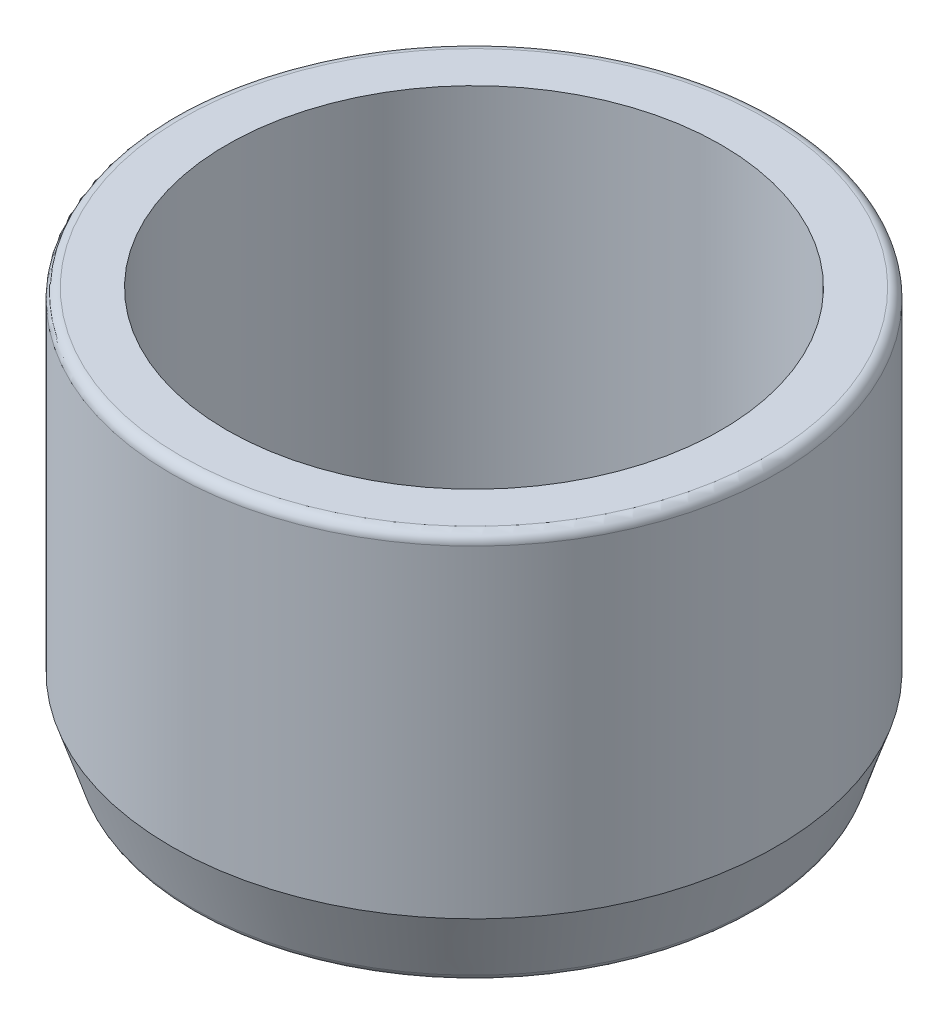
SolidWorks part; units mm, degrees
ref_plane "Front Plane" through (0, 0, 0) normal (0, 0, 1) x (1, 0, 0)
ref_plane "Top Plane" through (0, 0, 0) normal (0, 1, 0) x (1, 0, 0)
ref_plane "Right Plane" through (0, 0, 0) normal (1, 0, 0) x (0, 0, -1)
sketch "Sketch1" plane through (0, 0, 0) normal (0, 1, 0) x (1, 0, 0)
  circle A0 centre (0, 0) radius 30
  circle A1 centre (0, 0) radius 24.5
  dimension "D1" = 49
  dimension "D2" = 60
extrude "Boss-Extrude1" add sketch "Sketch1" along normal mid plane 40
chamfer "Chamfer2" distance 2.31 distance2 7 1 edges at (0, -20, 30) first distance on face at (0, -20, 30)
fillet "Fillet1" radius 1 2 edges at (0, -20, 27.69) (0, 20, 30)
